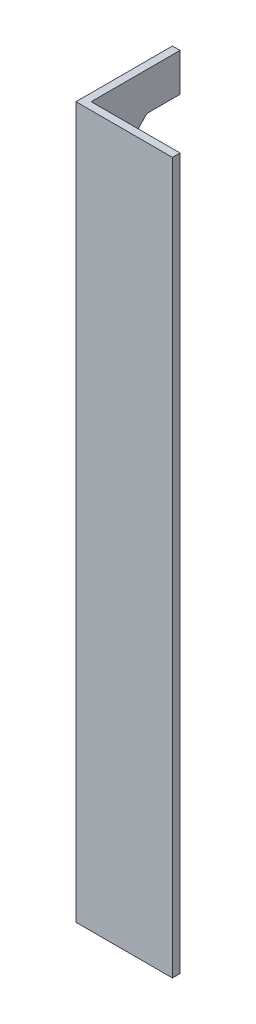
SolidWorks part; units mm, degrees
ref_plane "Alzado" through (0, 0, 0) normal (0, 0, 1) x (1, 0, 0)
ref_plane "Planta" through (0, 0, 0) normal (0, 1, 0) x (1, 0, 0)
ref_plane "Vista lateral" through (0, 0, 0) normal (1, 0, 0) x (0, 0, -1)
sketch "Croquis1" plane through (0, 0, 0) normal (0, 1, 0) x (1, 0, 0)
  line L0 (0, 0) -> (0, 38)
  line L1 (0, 0) -> (38, 0)
  line L2 (3, 3) -> (38, 3)
  line L3 (3, 3) -> (3, 38)
  line L4 (0, 38) -> (3, 38)
  line L5 (38, 3) -> (38, 0)
  dimension "D1" = 38
  dimension "D2" = 3
extrude "Saliente-Extruir1" add sketch "Croquis1" along normal blind 280
sketch "Croquis2" plane through (0, 0, 0) normal (-1, 0, 0) x (0, 0, 1)
  line L0 (-15, 0) -> (-15, 280) construction
  line L1 (-38, 0) -> (0, 0) construction
  line L2 (-38, 280) -> (0, 280) construction
  line L3 (-38, 280) -> (-38, 0) construction
  line L4 (0, 280) -> (0, 0) construction
  line L5 (-38, 15) -> (-15, 15)
  line L6 (-38, 280) -> (-38, 0) construction
  line L7 (-15, 15) -> (-15, 265)
  line L8 (-15, 265) -> (-38, 265)
  line L9 (-38, 15) -> (-38, 265)
  point P14 (-5.5988, 114.1473)
  dimension "D1" = 15
  dimension "D2" = 15
  dimension "D3" = 15
extrude "Cortar-Extruir1" cut sketch "Croquis2" against normal up to surface (3 mm away) up to face at (3, 140, -20.5)
chamfer "Chaflán1" distance 10 angle 45 2 edges at (1.5, 15, -15) (1.5, 265, -15)
